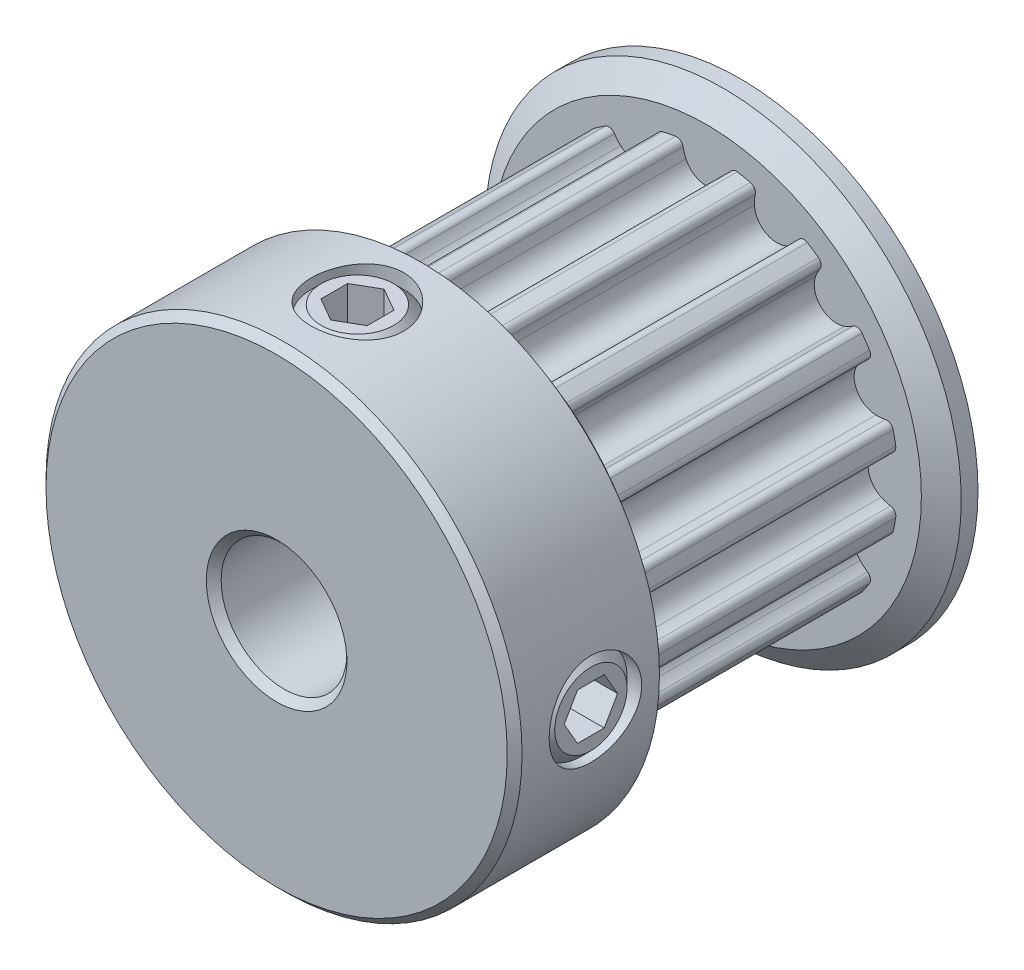
SolidWorks part; units mm, degrees
ref_plane "Front Plane" through (0, 0, 0) normal (0, 0, 1) x (1, 0, 0)
ref_plane "Top Plane" through (0, 0, 0) normal (0, 1, 0) x (1, 0, 0)
ref_plane "Right Plane" through (0, 0, 0) normal (1, 0, 0) x (0, 0, -1)
sketch "Sketch1" plane through (0, 0, 0) normal (0, 0, 1) x (1, 0, 0)
  line L1 (-2.553, 6.1245) -> (2.553, 6.1245) construction
  line L4 (0, 0) -> (0, 6.1245) construction
  line L5 (0, 6.1245) -> (0, 12.0668) construction
  line L6 (0, 7.6455) -> (2.9417, 7.0569) construction
  line L7 (2.9417, 7.0569) -> (3.8741, 6.6682) construction
  line L8 (2.9417, 7.0569) -> (2.553, 6.1245) construction
  line L9 (-2.9417, 7.0569) -> (-2.553, 6.1245) construction
  line L10 (-2.7951, 6.7052) -> (-3.7579, 9.015)
  line L11 (-3.7579, 9.015) -> (3.7579, 9.015)
  line L12 (3.7579, 9.015) -> (2.7951, 6.7052)
  circle A0 centre (0, 0) radius 7.6455 construction
  circle A1 centre (0, 0) radius 9.015 construction
  circle A2 centre (0, 0) radius 7.2645 construction
  arc A3 (-0.7739, 6.6229) -> (0.7739, 6.6229) centre (0, 6.9745) ccw
  arc A4 (-0.7739, 6.6229) -> (-0.8836, 6.9694) centre (0.61, 7.2516) cw
  arc A5 (-2.7951, 6.7052) -> (-1.1695, 7.1697) centre (0, 0) cw
  arc A6 (-0.8836, 6.9694) -> (-1.1695, 7.1697) centre (-1.1292, 6.923) ccw
  arc A7 (2.7951, 6.7052) -> (1.1695, 7.1697) centre (0, 0) ccw
  arc A8 (0.8836, 6.9694) -> (1.1695, 7.1697) centre (1.1292, 6.923) cw
  arc A9 (0.7739, 6.6229) -> (0.8836, 6.9694) centre (-0.61, 7.2516) ccw
  point P6 (0, 20.9083)
  point P11 (0, 7.6455)
  point P13 (0, 9.015)
  point P14 (0, 7.2645)
  dimension "D1" = 8.8416
  dimension "D2" = 4.4213
sketch "Sketch2" plane through (0, 0, 0) normal (1, 0, 0) x (0, 0, -1)
  line L0 (-8.775, 2.3812) -> (8.775, 2.3812)
  line L1 (-8.775, 2.3812) -> (-8.775, 9.015)
  line L2 (-3.29, 9.015) -> (-8.775, 9.015)
  line L3 (-3.925, 2.3813) -> (-3.925, 9.015) construction
  line L4 (-3.925, 9.015) -> (-2.655, 9.015) construction
  line L5 (-2.655, 9.015) -> (-2.655, 7.2645) construction
  line L6 (-2.655, 7.2645) -> (7.505, 7.2645)
  line L7 (7.505, 7.2645) -> (7.505, 9.015) construction
  line L8 (7.505, 9.015) -> (8.775, 9.015) construction
  line L9 (8.775, 9.015) -> (8.775, 2.3812)
  line L10 (-8.775, 0) -> (8.775, 0) construction
  line L11 (8.14, 9.015) -> (7.505, 8.1398)
  line L12 (-2.655, 8.1398) -> (-3.29, 9.015)
  line L14 (-2.655, 8.1398) -> (-2.655, 7.2645)
  line L15 (7.505, 7.2645) -> (7.505, 8.1398)
  line L16 (8.14, 9.015) -> (8.775, 9.015)
  arc A0 (-2.655, 8.1398) -> (-3.29, 9.015) centre (-3.5757, 8.1398) ccw construction
  arc A1 (7.505, 8.1398) -> (8.14, 9.015) centre (8.4257, 8.1398) cw construction
  point P12 (-2.655, 8.1398)
  point P14 (-3.29, 9.015)
  point P20 (7.505, 8.1398)
  point P21 (8.14, 9.015)
  point P25 (7.505, 0)
  point P26 (-2.655, 0)
  dimension "OA" = 17.55
  dimension "Bore" = 4.7625
  dimension "Outside Width" = 11.43
  dimension "Inside Width" = 10.16
revolve "Revolve1" add sketch "Sketch2" angle 360 mid plane about L10
sketch "Sketch3" plane through (0, 0, 0) normal (0, 0, 1) x (1, 0, 0)
  line L6 (3.7579, 9.015) -> (-3.7579, 9.015)
  line L7 (2.7951, 6.7052) -> (3.7579, 9.015)
  line L8 (-3.7579, 9.015) -> (-2.7951, 6.7052)
  line L9 (3.7579, 9.015) -> (-3.7579, 9.015)
  line L10 (2.7951, 6.7052) -> (3.7579, 9.015)
  line L11 (-3.7579, 9.015) -> (-2.7951, 6.7052)
  arc A8 (2.7951, 6.7052) -> (1.1695, 7.1697) centre (0, 0) ccw
  arc A9 (1.1695, 7.1697) -> (0.8836, 6.9694) centre (1.1292, 6.923) ccw
  arc A10 (0.7739, 6.6229) -> (0.8836, 6.9694) centre (-0.61, 7.2516) ccw
  arc A11 (-0.7739, 6.6229) -> (0.7739, 6.6229) centre (0, 6.9745) ccw
  arc A12 (-0.8836, 6.9694) -> (-0.7739, 6.6229) centre (0.61, 7.2516) ccw
  arc A13 (-0.8836, 6.9694) -> (-1.1695, 7.1697) centre (-1.1292, 6.923) ccw
  arc A14 (-1.1695, 7.1697) -> (-2.7951, 6.7052) centre (0, 0) ccw
  arc A15 (2.7951, 6.7052) -> (1.1695, 7.1697) centre (0, 0) ccw
  arc A16 (1.1695, 7.1697) -> (0.8836, 6.9694) centre (1.1292, 6.923) ccw
  arc A17 (0.7739, 6.6229) -> (0.8836, 6.9694) centre (-0.61, 7.2516) ccw
  arc A18 (-0.7739, 6.6229) -> (0.7739, 6.6229) centre (0, 6.9745) ccw
  arc A19 (-0.8836, 6.9694) -> (-0.7739, 6.6229) centre (0.61, 7.2516) ccw
  arc A20 (-0.8836, 6.9694) -> (-1.1695, 7.1697) centre (-1.1292, 6.923) ccw
  arc A21 (-1.1695, 7.1697) -> (-2.7951, 6.7052) centre (0, 0) ccw
  dimension "D1" = 0
extrude "Cut-Extrude1" cut sketch "Sketch3" against normal up to vertex (7.505 mm away) from vertex up to point (0, 7.2645, -7.505) starting at point (0, 7.2645, 2.655)
pattern_circular "CirPattern1" count 16 over 360 about axis through (0, 0, 8.775) along (0, 0, 1) of "Cut-Extrude1"
sketch "Sketch4" plane through (0, 0, 0) normal (1, 0, 0) x (0, -1, 0)
  line L0 (0, -2.655) -> (0, -8.775) construction
  line L1 (-2.3812, -8.775) -> (2.3812, -8.775) construction
  line L2 (8.1398, -2.655) -> (-8.1398, -2.655) construction
  circle A0 centre (0, -5.715) radius 1.7526
extrude "Cut-Extrude2" cut sketch "Sketch4" along normal through all
ref_plane "Plane1" through (0, 0, 5.715) normal (0, 0, 1) x (1, 0, 0)
sketch "Sketch5" plane through (0, 0, 5.715) normal (0, 0, 1) x (1, 0, 0)
  line L0 (0, 0) -> (0, 9.015) construction
  line L1 (2.3812, -1.3716) -> (2.3812, 0)
  line L2 (2.7622, -1.7526) -> (8.462, -1.7526)
  line L3 (2.3812, 0) -> (9.015, 0) construction
  line L4 (2.3812, 0) -> (8.843, 0)
  line L5 (8.843, 0) -> (8.843, -1.3716)
  line L6 (2.7622, -1.7526) -> (2.3812, -1.3716)
  line L7 (8.843, -1.3716) -> (8.462, -1.7526)
  circle A0 centre (0, 0) radius 9.015 construction
  circle A1 centre (0, 0) radius 2.3812 construction
  point P2 (2.3812, -1.7526)
  point P11 (8.843, -1.7526)
revolve "Revolve2" add sketch "Sketch5" angle 360 mid plane about L4
sketch "Sketch6" plane through (8.843, 5.3841, 0) normal (-1, 0, 0) x (0, -1, 0)
  line L1 (5.3841, 6.7269) -> (4.5078, 6.2209)
  line L2 (4.5078, 6.2209) -> (4.5078, 5.2091)
  line L3 (4.5078, 5.2091) -> (5.3841, 4.7031)
  line L4 (5.3841, 4.7031) -> (6.2604, 5.2091)
  line L5 (6.2604, 5.2091) -> (6.2604, 6.2209)
  line L6 (6.2604, 6.2209) -> (5.3841, 6.7269)
  circle A0 centre (5.3841, 5.715) radius 0.8763 construction
  dimension "D1" = 1.7526
extrude "Cut-Extrude3" cut sketch "Sketch6" along normal blind 1.3144
pattern_circular "CirPattern3" count 2 over 90 about axis through (0, 0, 8.775) along (0, 0, 1) of "Cut-Extrude2", "Revolve2", "Cut-Extrude3"
chamfer "Chamfer1" distance 0.2807 angle 45 2 edges at (2.3812, 0, 8.775) (9.015, 0, 8.775)
ref_axis "Center Axis 1" through (0, 0, -8.775) along (0, 0, 1)
ref_plane "Contact Plane 1" through (0, 0, 8.775) normal (0, 0, 1) x (1, 0, 0)
ref_plane "Contact Plane 2" through (0, 0, -8.775) normal (0, 0, -1) x (-1, 0, 0)
equation "\"D2@Sketch1\"= \"D1@Sketch1\" / 2"
equation "\"D1@Sketch6\" = \"Set Screw@Sketch4\" / 2"
equation "\"D1@Cut-Extrude3\" = \"D1@Sketch6\"*.75"
